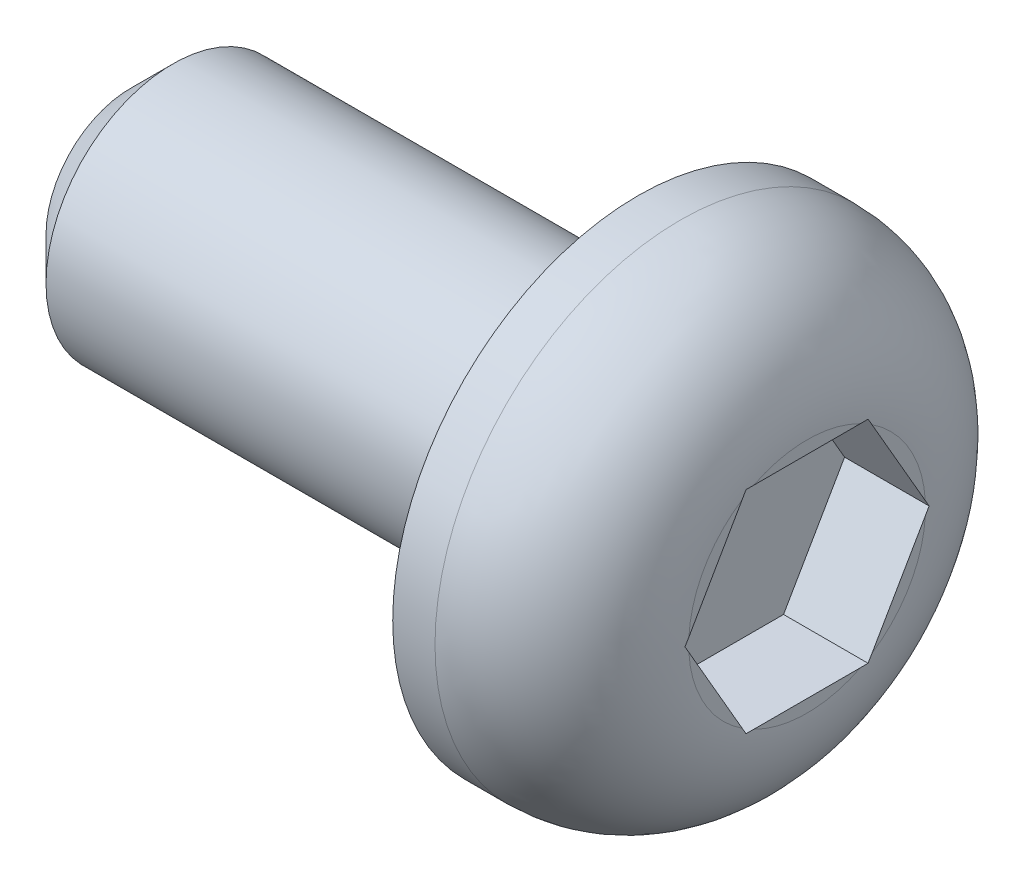
SolidWorks part; units mm, degrees
ref_plane "Front Plane" through (0, 0, 0) normal (0, 0, 1) x (1, 0, 0)
ref_plane "Top Plane" through (0, 0, 0) normal (0, 1, 0) x (1, 0, 0)
ref_plane "Right Plane" through (0, 0, 0) normal (1, 0, 0) x (0, 0, -1)
sketch "Sketch1" plane through (0, 0, 0) normal (0, 1, 0) x (1, 0, 0)
  line L1 (0, 0) -> (-6, 0)
  line L2 (0, 0) -> (0, -1.5)
  line L3 (0, -1.5) -> (-6, -1.5)
  line L4 (-6, 0) -> (-6, -1.5)
  line L5 (0, -1.5) -> (2, -1.5)
  line L6 (0, -1.5) -> (0, 1.4)
  line L7 (0, 1.4) -> (2, 1.4)
  line L8 (2, -1.5) -> (2, 1.4)
  dimension "D1" = 2
  dimension "D2" = 2.9
  dimension "D3" = 1.5
  dimension "D4" = 6
revolve "Revolve1" add sketch "Sketch1" angle 360 about L3 region at (-3, 0, 0.75) region at (1, 0, 0.05)
ref_point "Point1"
sketch "Sketch3" plane through (2, 0, 0) normal (1, 0, 0) x (0, 0, -1)
  line L1 (-2.2217, -1.25) -> (-0.7783, -1.25)
  line L2 (-0.7783, -1.25) -> (-0.0566, 0)
  line L3 (-0.0566, 0) -> (-0.7783, 1.25)
  line L4 (-0.7783, 1.25) -> (-2.2217, 1.25)
  line L5 (-2.2217, 1.25) -> (-2.9434, 0)
  line L6 (-2.9434, 0) -> (-2.2217, -1.25)
  circle A0 centre (-1.5, 0) radius 1.25 construction
  dimension "D1" = 2.5
extrude "Cut-Extrude1" cut sketch "Sketch3" against normal blind 1
fillet "Fillet1" radius 1.5 1 edges at (2, 0, -1.4)
chamfer "Chamfer1" distance 0.5 angle 45 1 edges at (-6, 0, 0)
